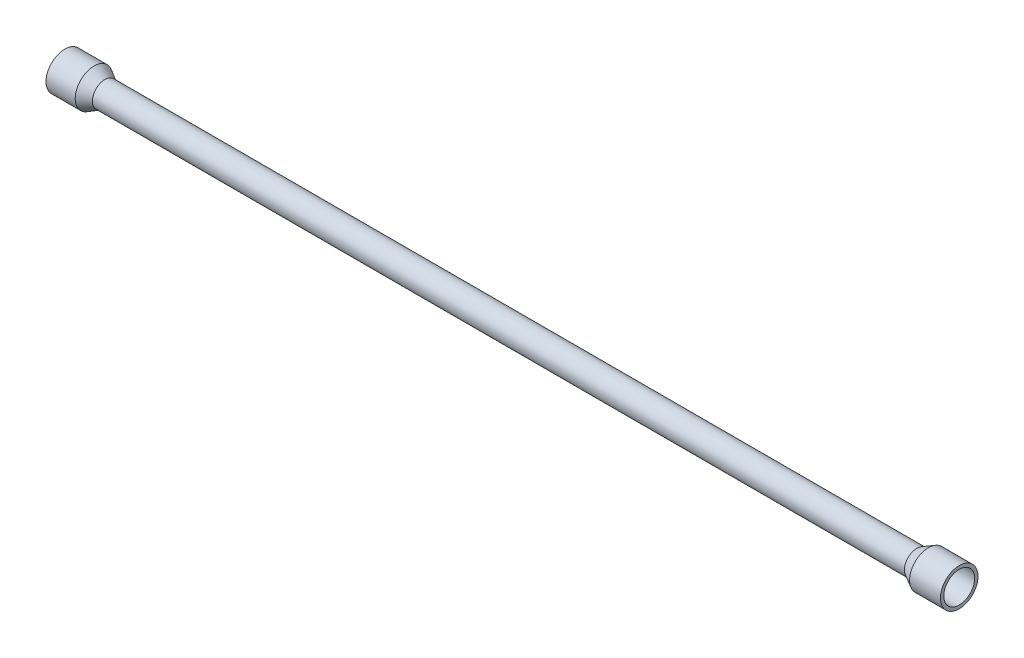
SolidWorks part; units mm, degrees
ref_plane "Front Plane" through (0, 0, 0) normal (0, 0, 1) x (1, 0, 0)
ref_plane "Top Plane" through (0, 0, 0) normal (0, 1, 0) x (1, 0, 0)
ref_plane "Right Plane" through (0, 0, 0) normal (1, 0, 0) x (0, 0, -1)
sketch "Sketch1" plane through (0, 0, 0) normal (1, 0, 0) x (0, 0, -1)
  circle A0 centre (0, 0) radius 75
  circle A1 centre (0, 0) radius 37.5
  dimension "D1" = 150
  dimension "D2" = 75
extrude "Boss-Extrude1" add sketch "Sketch1" along normal blind 5000
sketch "Sketch2" plane through (5000, 0, 0) normal (1, 0, 0) x (0, 0, -1)
  circle A0 centre (0, 0) radius 112.5
  circle A1 centre (0, 0) radius 92.5
  dimension "D1" = 225
  dimension "D2" = 185
extrude "Boss-Extrude2" add sketch "Sketch2" along normal blind 185 separate body
sketch "Sketch4" plane through (0, 0, 0) normal (0, 0, 1) x (1, 0, 0)
  line L0 (5000, 112.5) -> (4931.2705, 75)
  line L1 (5000, 75) -> (0, 75) construction
  line L2 (4931.2705, 75) -> (5000, 75)
  line L3 (5000, 75) -> (5000, 112.5)
  line L4 (5128.6321, 0) -> (4589.2172, 0) construction
  line L5 (5000, 75) -> (0, 75) construction
  point P10 (4931.2705, 75)
revolve "Revolve1" add sketch "Sketch4" angle 360 about L4
sketch "Sketch6" plane through (0, 0, 0) normal (-1, 0, 0) x (0, 0, 1)
  circle A0 centre (0, 0) radius 87.5
  circle A1 centre (0, 0) radius 112.5
  dimension "D1" = 175
  dimension "D2" = 225
extrude "Boss-Extrude3" add sketch "Sketch6" along normal blind 175 separate body
sketch "Sketch7" plane through (0, 0, 0) normal (0, 0, 1) x (1, 0, 0)
  line L0 (0, 0) -> (-301.92, 0) construction
  line L1 (0, 112.5) -> (65.3632, 75)
  line L2 (4931.2705, 75) -> (0, 75) construction
  line L3 (65.3632, 75) -> (0, 75)
  line L4 (0, 75) -> (0, 112.5)
revolve "Revolve2" add sketch "Sketch7" angle 360 about L0
